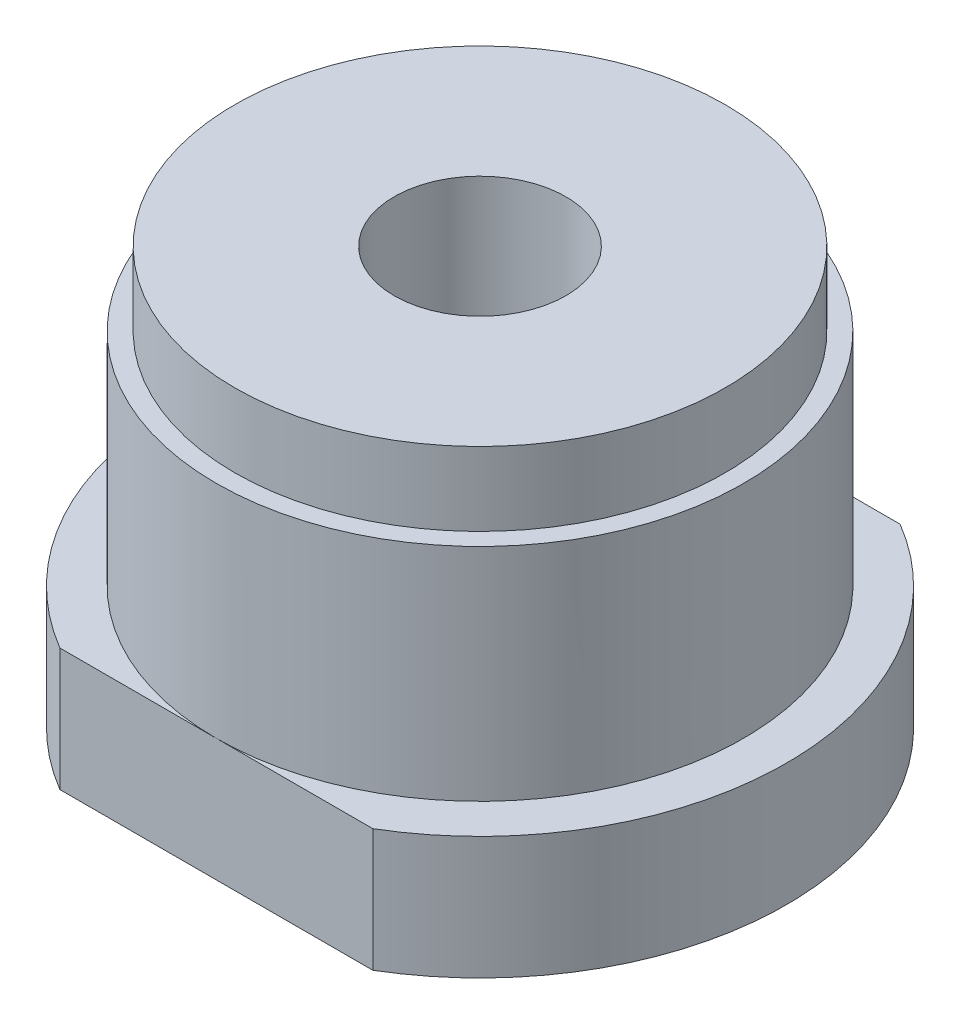
SolidWorks part; units mm, degrees
ref_plane "Front Plane" through (0, 0, 0) normal (0, 0, 1) x (1, 0, 0)
ref_plane "Top Plane" through (0, 0, 0) normal (0, 1, 0) x (1, 0, 0)
ref_plane "Right Plane" through (0, 0, 0) normal (1, 0, 0) x (0, 0, -1)
sketch "Sketch1" plane through (0, 0, 0) normal (0, 1, 0) x (1, 0, 0)
  circle A0 centre (0, 0) radius 12.5
  dimension "D1" = 25
extrude "Boss-Extrude1" add sketch "Sketch1" along normal blind 17
sketch "Sketch2" plane through (0, 17, 0) normal (0, 1, 0) x (1, 0, 0)
  circle A0 centre (0, 0) radius 3.5
  dimension "D1" = 7
extrude "Cut-Extrude1" cut sketch "Sketch2" against normal offset from surface (15 mm away) 2 up to face at (0, 0, 12.5)
sketch "Sketch3" plane through (0, 0, 0) normal (1, 0, 0) x (0, 0, -1)
  line L0 (0, 9.35) -> (0, -9.35) construction
  line L1 (11.825, 0) -> (-11.825, 0) construction
  circle A0 centre (8, 3) radius 1.5
  dimension "D1" = 3
  dimension "D2" = 8
  dimension "D3" = 3
extrude "Cut-Extrude2" [suppressed] cut sketch "Sketch3" against normal through all and the other way through all
mirror "Mirror1" [suppressed] about plane through (0, 0, 0) normal (0, 0, 1)
sketch "Sketch4" plane through (0, 17, 0) normal (0, 1, 0) x (1, 0, 0)
  circle A0 centre (0, 0) radius 10
  dimension "D1" = 20
extrude "Cut-Extrude3" cut sketch "Sketch4" against normal offset from surface (12 mm away) 5 flip side to cut up to face at (0, 0, 12.5)
sketch "Sketch5" plane through (0, 0, 0) normal (0, -1, 0) x (1, 0, 0)
  line L0 (9.35, 0) -> (-9.35, 0) construction
  circle A0 centre (-8, 0) radius 1.25
  dimension "D1" = 2.5
  dimension "D2" = 8
extrude "Cut-Extrude4" cut sketch "Sketch5" against normal blind 10
mirror "Mirror2" about plane through (0, 0, 0) normal (1, 0, 0) of "Cut-Extrude4"
sketch "Sketch6" plane through (0, 5, 0) normal (0, 1, 0) x (1, 0, 0)
  line L0 (0, -9.35) -> (0, 9.35) construction
  circle A0 centre (0, 12.5) radius 2.5
  circle A1 centre (0, 0) radius 10 construction
  dimension "D1" = 5
extrude "Cut-Extrude5" [suppressed] cut sketch "Sketch6" against normal blind 5
sketch "Sketch8" plane through (0, 5, 0) normal (0, 1, 0) x (1, 0, 0)
  circle A0 centre (0, 0) radius 10.75
  circle A1 centre (0, 0) radius 4
  dimension "D1" = 21.5
extrude "Boss-Extrude3" add sketch "Sketch8" along normal blind 9
sketch "Sketch7" plane through (0, 5, 0) normal (0, 1, 0) x (1, 0, 0)
  line L1 (-11.0868, 15.6344) -> (11.839, 15.6344)
  line L2 (-11.0868, 15.6344) -> (-11.0868, 10.75)
  line L3 (-11.0868, 10.75) -> (11.839, 10.75)
  line L4 (11.839, 15.6344) -> (11.839, 10.75)
  circle A0 centre (0, 0) radius 10.75 construction
extrude "Cut-Extrude6" cut sketch "Sketch7" against normal through all
mirror "Mirror3" about plane through (0, 0, 0) normal (0, 0, 1) of "Cut-Extrude6"
pattern_circular "CirPattern1" [suppressed] count 12 over 360 of bodies 109
fillet "Fillet1" [suppressed] radius 1
